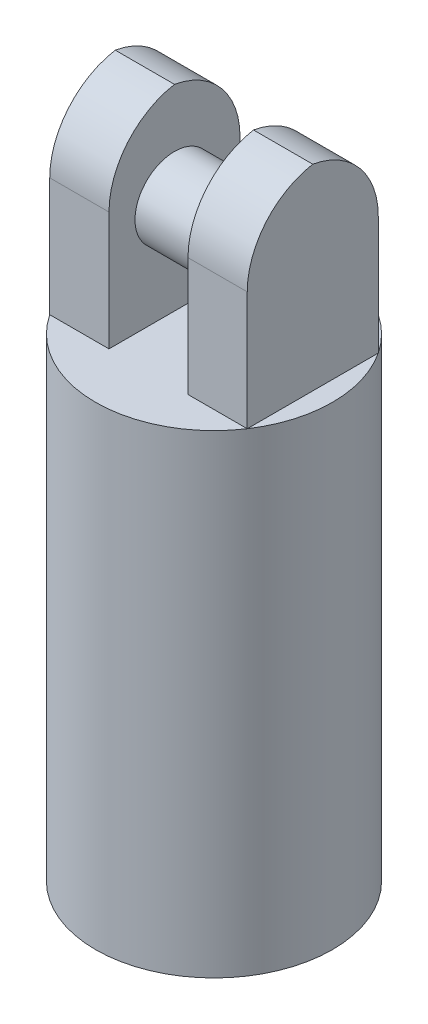
SolidWorks part; units mm, degrees
ref_plane "Front Plane" through (0, 0, 0) normal (0, 0, 1) x (1, 0, 0)
ref_plane "Top Plane" through (0, 0, 0) normal (0, 1, 0) x (1, 0, 0)
ref_plane "Right Plane" through (0, 0, 0) normal (1, 0, 0) x (0, 0, -1)
sketch "Sketch1" plane through (0, 0, 0) normal (0, 1, 0) x (1, 0, 0)
  circle A0 centre (0, 0) radius 38.1
  dimension "D1" = 76.2
extrude "Boss-Extrude1" add sketch "Sketch1" along normal blind 152.4
sketch "Sketch2" plane through (0, 152.4, 0) normal (0, 1, 0) x (1, 0, 0)
  line L1 (-31.75, -21.0606) -> (31.75, -21.0606)
  line L2 (-31.75, -21.0606) -> (-31.75, 21.0606)
  line L3 (-31.75, 21.0606) -> (31.75, 21.0606)
  line L4 (31.75, -21.0606) -> (31.75, 21.0606)
  line L5 (-31.75, -21.0606) -> (31.75, 21.0606) construction
  line L6 (-31.75, 21.0606) -> (31.75, -21.0606) construction
  circle A0 centre (0, 0) radius 38.1 construction
  point P0 (0, 0)
  dimension "D1" = 63.5
extrude "Boss-Extrude2" add sketch "Sketch2" along normal blind 63.5
sketch "Sketch3" plane through (0, 215.9, 0) normal (0, 1, 0) x (1, 0, 0)
  line L0 (31.75, 21.0606) -> (-31.75, 21.0606) construction
  line L1 (-12.7, -21.0606) -> (12.7, -21.0606)
  line L2 (-12.7, -21.0606) -> (-12.7, 21.0606)
  line L3 (-12.7, 21.0606) -> (12.7, 21.0606)
  line L4 (12.7, -21.0606) -> (12.7, 21.0606)
  line L5 (-12.7, -21.0606) -> (12.7, 21.0606) construction
  line L6 (-12.7, 21.0606) -> (12.7, -21.0606) construction
  point P0 (0, 0)
  dimension "D1" = 25.4
extrude "Cut-Extrude1" cut sketch "Sketch3" against normal blind 63.5
sketch "Sketch4" plane through (31.75, 0, 0) normal (1, 0, 0) x (0, 0, -1)
  circle A0 centre (0, 184.15) radius 12.7
fillet "Fillet1" radius 25.4 4 edges at (-22.225, 215.9, -21.0606) (-22.225, 215.9, 21.0606) (22.225, 215.9, -21.0606) (22.225, 215.9, 21.0606)
sketch "Sketch5" plane through (0, 0, 0) normal (0, -1, 0) x (1, 0, 0)
  circle A0 centre (0, 0) radius 25.4
extrude "Cut-Extrude3" cut sketch "Sketch5" against normal blind 50.8
extrude "Boss-Extrude3" add sketch "Sketch4" against normal blind 52.578 contours A0
